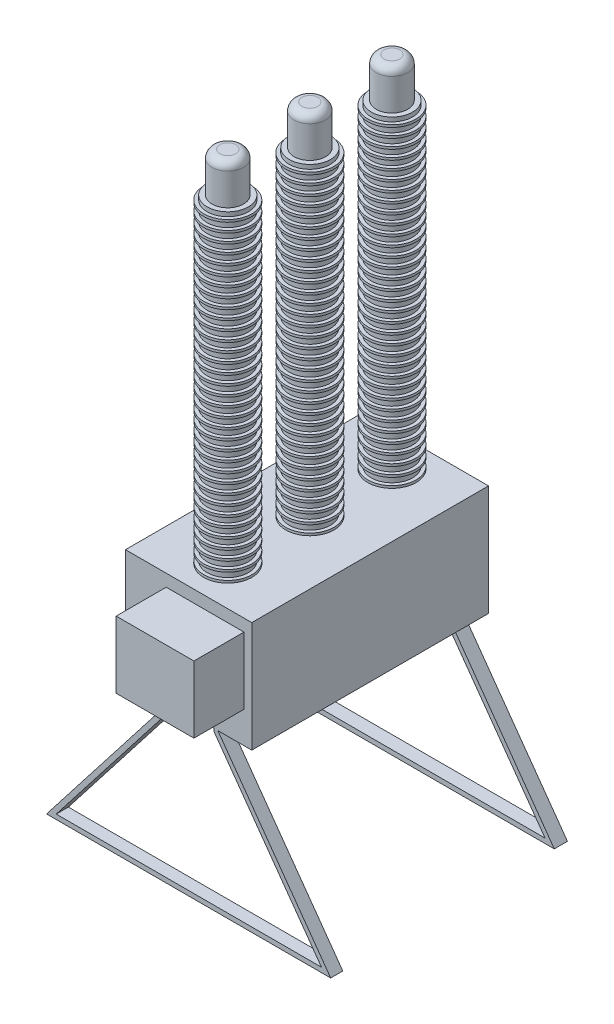
SolidWorks part; units mm, degrees
ref_plane "Alzado" through (0, 0, 0) normal (0, 0, 1) x (1, 0, 0)
ref_plane "Planta" through (0, 0, 0) normal (0, 1, 0) x (1, 0, 0)
ref_plane "Vista lateral" through (0, 0, 0) normal (1, 0, 0) x (0, 0, -1)
sketch "Croquis1" plane through (0, 0, 0) normal (0, 0, 1) x (1, 0, 0)
  line L1 (-400, 350) -> (400, 350)
  line L2 (-400, 350) -> (-400, -350)
  line L3 (-400, -350) -> (400, -350)
  line L4 (400, 350) -> (400, -350)
  line L5 (-400, 350) -> (400, -350) construction
  line L6 (-400, -350) -> (400, 350) construction
  point P0 (0, 0)
  dimension "D1" = 800
  dimension "D2" = 700
extrude "Saliente-Extruir1" add sketch "Croquis1" along normal blind 1500
ref_plane "Plano1" through (0, 0, 750) normal (0, 0, 1) x (1, 0, 0)
sketch "Croquis2" plane through (0, 0, 750) normal (0, 0, 1) x (1, 0, 0)
  line L0 (0, -350) -> (0, -1350) construction
  line L1 (-400, -350) -> (400, -350) construction
  line L2 (-122.3886, -350) -> (-900, -1350)
  line L3 (-900, -1350) -> (900, -1350)
  line L4 (900, -1350) -> (185.244, -350)
  line L5 (-98.7061, -368.4158) -> (-838.6689, -1320)
  line L6 (-838.6689, -1320) -> (841.682, -1320)
  line L7 (841.682, -1320) -> (160.8374, -367.4447)
  line L8 (-98.7061, -368.4158) -> (-98.7061, -350)
  line L9 (160.8374, -367.4447) -> (160.8374, -350)
  line L10 (160.8374, -350) -> (185.244, -350)
  line L11 (-98.7061, -350) -> (-122.3886, -350)
  dimension "D1" = 1000
  dimension "D2" = 900
  dimension "D3" = 900
  dimension "D4" = 30
extrude "Saliente-Extruir2" add sketch "Croquis2" against normal blind 750 and the other way blind 750
ref_plane "Plano2" through (-1150, 0, 0) normal (-1, 0, 0) x (0, 0, 1)
sketch "Croquis3" plane through (-1150, 0, 0) normal (-1, 0, 0) x (0, 0, 1)
  line L0 (83.4056, -350) -> (83.4056, -1519.7317)
  line L1 (1500, -350) -> (0, -350) construction
  line L2 (83.4056, -1519.7317) -> (1423.1161, -1519.7317)
  line L3 (1423.1161, -1519.7317) -> (1423.1161, -350)
  line L4 (1500, -350) -> (0, -350) construction
  line L5 (1423.1161, -350) -> (83.4056, -350)
  point P5 (83.4056, -1519.7317)
extrude "Cortar-Extruir1" cut sketch "Croquis3" against normal blind 2289
sketch "Croquis4" plane through (0, 0, 1500) normal (0, 0, 1) x (1, 0, 0)
  line L1 (-141.9477, 273.1163) -> (350.5929, 273.1163)
  line L2 (-141.9477, 273.1163) -> (-141.9477, -150.4687)
  line L3 (-141.9477, -150.4687) -> (350.5929, -150.4687)
  line L4 (350.5929, 273.1163) -> (350.5929, -150.4687)
  line L5 (-141.9477, 273.1163) -> (350.5929, -150.4687) construction
  line L6 (-141.9477, -150.4687) -> (350.5929, 273.1163) construction
  point P0 (104.3226, 61.3238)
extrude "Saliente-Extruir3" add sketch "Croquis4" along normal blind 317
sketch "Croquis5" plane through (0, 350, 0) normal (0, 1, 0) x (1, 0, 0)
  circle A0 centre (0, -211.8388) radius 130.6182
  circle A1 centre (0, -731.8388) radius 130.6182
  circle A2 centre (0, -1251.8388) radius 130.6182
  dimension "D1" = 3
extrude "Saliente-Extruir4" add sketch "Croquis5" along normal blind 2022
sketch "Croquis6" plane through (0, 350, 0) normal (0, 1, 0) x (1, 0, 0)
  circle A0 centre (0, -211.8388) radius 152.5728
extrude "Saliente-Extruir5" add sketch "Croquis6" along normal blind 15
pattern_linear "MatrizL1" count 34 spacing 60 along (0, 1, 0) of "Saliente-Extruir5"
pattern_linear "MatrizL2" count 3 spacing 520 along (0, 0, 1) of "MatrizL1"
sketch "Croquis7" plane through (0, 2372, 0) normal (0, 1, 0) x (1, 0, 0)
  circle A0 centre (0, -211.8388) radius 99.9421
extrude "Saliente-Extruir6" add sketch "Croquis7" along normal blind 251
fillet "Redondeo1" radius 50 1 edges at (0, 2623, 311.781)
pattern_linear "MatrizL5" count 3 spacing 520 along (0, 0, 1) of "Redondeo1", "Saliente-Extruir6"
